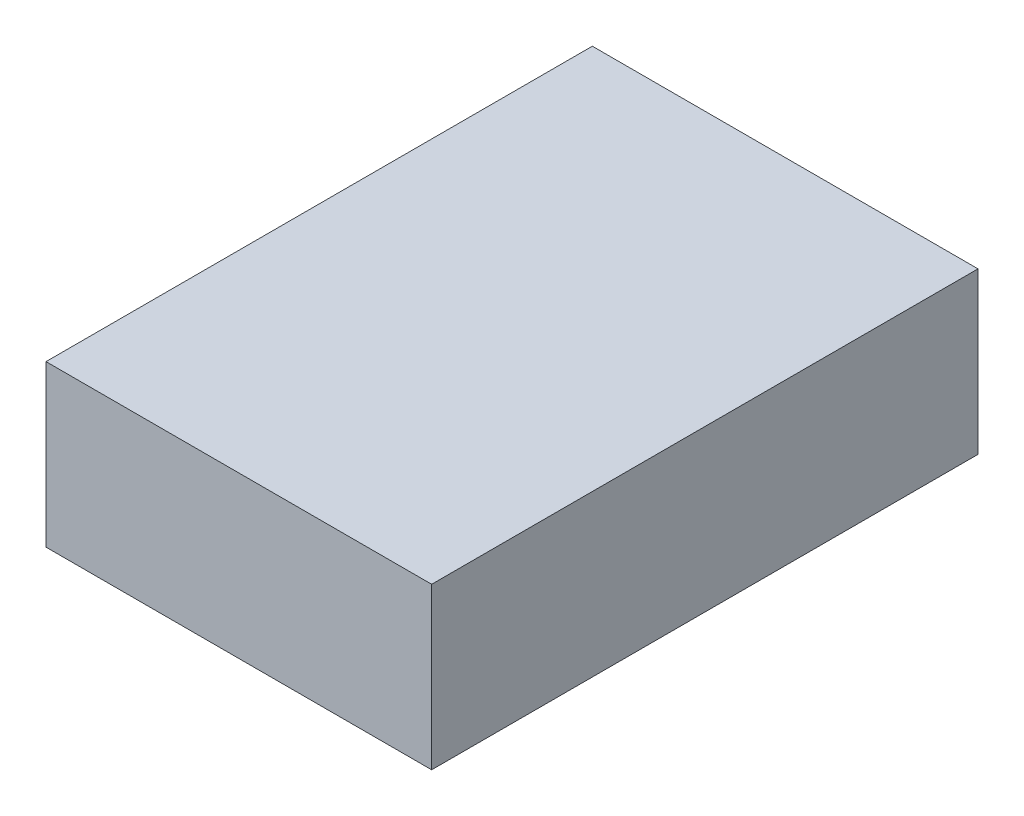
SolidWorks part; units mm, degrees
ref_plane "Front Plane" through (0, 0, 0) normal (0, 0, 1) x (1, 0, 0)
ref_plane "Top Plane" through (0, 0, 0) normal (0, 1, 0) x (1, 0, 0)
ref_plane "Right Plane" through (0, 0, 0) normal (1, 0, 0) x (0, 0, -1)
sketch "SK_Envelope" plane through (0, 0, 0) normal (0, 1, 0) x (1, 0, 0)
  line L1 (-12, 17) -> (12, 17)
  line L2 (-12, 17) -> (-12, -17)
  line L3 (-12, -17) -> (12, -17)
  line L4 (12, 17) -> (12, -17)
  dimension "D1" = 34
  dimension "D2" = 24
  dimension "D3" = 17
  dimension "D4" = 12
extrude "EX_Envelope" add sketch "SK_Envelope" along normal blind 10
ref_axis "AX_X" through (0, 0, -18.7) along (0, 0, 1)
ref_axis "AX_Y" through (13.2, 0, 0) along (-1, 0, 0)
ref_axis "AX_Z" through (0, 10.5, 0) along (0, -1, 0)
